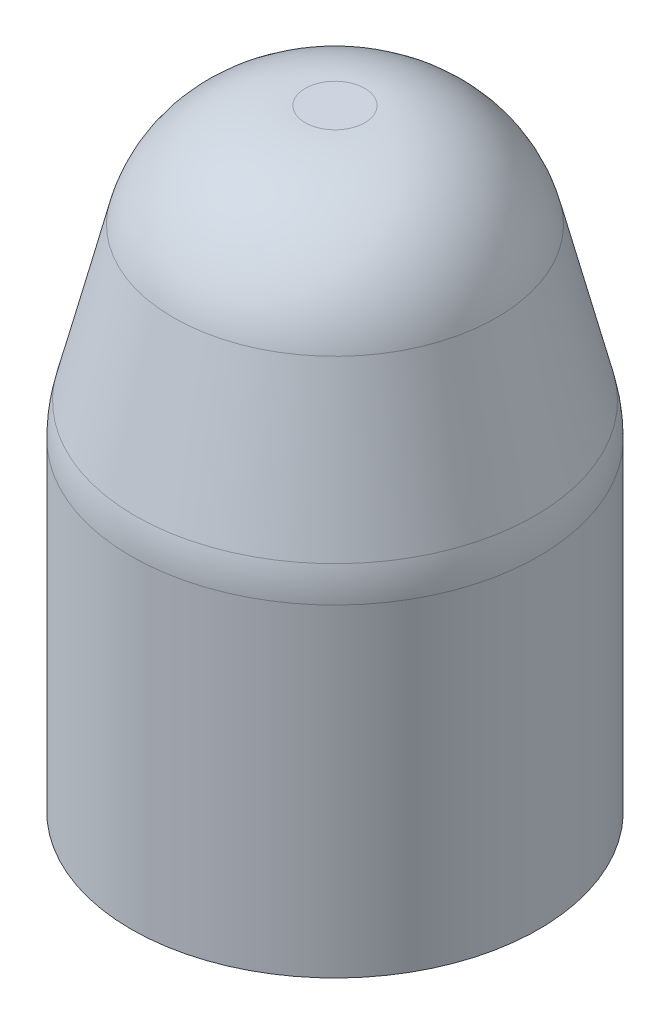
SolidWorks part; units mm, degrees
material "Glass"
ref_plane "Front Plane" through (0, 0, 0) normal (0, 0, 1) x (1, 0, 0)
ref_plane "Top Plane" through (0, 0, 0) normal (0, 1, 0) x (1, 0, 0)
ref_plane "Right Plane" through (0, 0, 0) normal (1, 0, 0) x (0, 0, -1)
ref_axis "Axis1" through (0, 9.45, 0) along (0, -1, 0)
sketch "Sketch1" plane through (0, 0, 0) normal (0, 0, 1) x (1, 0, 0)
  line L0 (0, 0) -> (3, 0)
  line L1 (3, 0) -> (3, 5)
  line L2 (0, 9) -> (2, 9)
  line L5 (2, 9) -> (3, 5)
  line L6 (0, 9) -> (0, 0)
  dimension "D1" = 9
  dimension "D2" = 5
  dimension "D3" = 2
  dimension "D4" = 3
revolve "Revolve1" add sketch "Sketch1" angle 360 about L6
fillet "Fillet1" radius 2 1 edges at (0, 9, 2)
fillet "Fillet2" radius 2 1 edges at (0, 5, 3)
